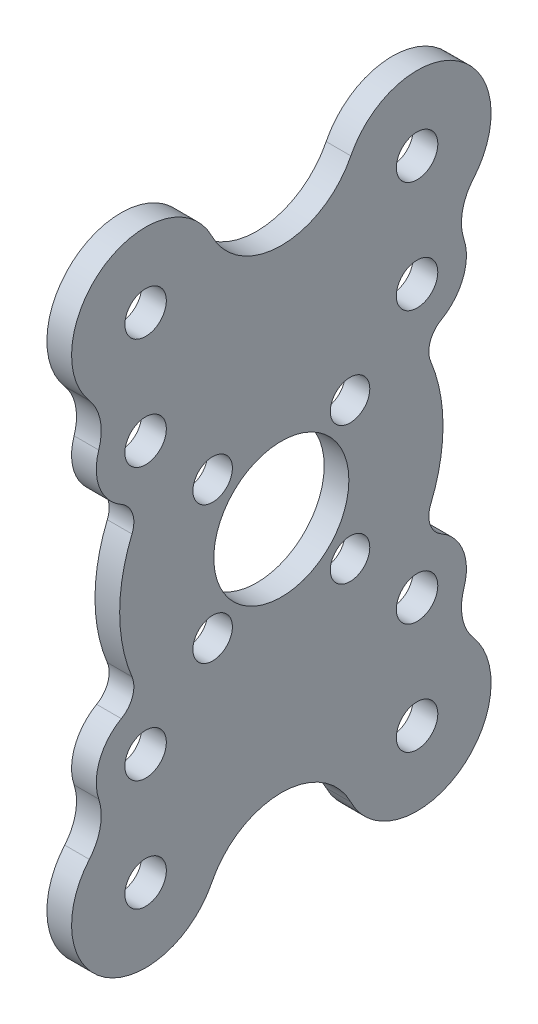
SolidWorks part; units mm, degrees
material "AR500"
ref_plane "Front Plane" through (0, 0, 0) normal (0, 0, 1) x (1, 0, 0)
ref_plane "Top Plane" through (0, 0, 0) normal (0, 1, 0) x (1, 0, 0)
ref_plane "Right Plane" through (0, 0, 0) normal (1, 0, 0) x (0, 0, -1)
ref_plane "Motor Front Plane" through (39.075, 0, 0) normal (1, 0, 0) x (0, 0, -1)
sketch "Sketch1" plane through (39.075, 0, 0) normal (1, 0, 0) x (0, 0, -1)
  line L0 (0, -17.4625) -> (0, 0) construction
  line L1 (17.4625, 17.4625) -> (-17.4625, 17.4625) construction
  line L2 (17.4625, 17.4625) -> (17.4625, -17.4625) construction
  line L3 (17.4625, -17.4625) -> (-17.4625, -17.4625) construction
  line L4 (-17.4625, 17.4625) -> (-17.4625, -17.4625) construction
  line L6 (17.4625, 0) -> (0, 0) construction
  circle A0 centre (8.8388, -8.8388) radius 1.65 construction
  circle A1 centre (8.8388, 8.8388) radius 1.65 construction
  circle A2 centre (-8.8388, -8.8388) radius 1.65 construction
  circle A3 centre (-8.8388, 8.8388) radius 1.65 construction
  circle A4 centre (8.8388, -8.8388) radius 1.65 construction
  circle A5 centre (8.8388, 8.8388) radius 1.65 construction
  circle A6 centre (-8.8388, -8.8388) radius 1.65 construction
  circle A7 centre (-8.8388, 8.8388) radius 1.65 construction
  circle A8 centre (0, 0) radius 20.8 construction
  circle A9 centre (0, 0) radius 8.69
  circle A10 centre (-8.8388, 8.8388) radius 2.54
  circle A11 centre (8.8388, 8.8388) radius 2.54
  circle A12 centre (8.8388, -8.8388) radius 2.54
  circle A13 centre (-8.8388, -8.8388) radius 2.54
  circle A14 centre (-8.8388, 8.8388) radius 3.81 construction
  circle A15 centre (17.4625, 17.4625) radius 3.8957 construction
  circle A16 centre (17.4625, 17.4625) radius 2.667
  circle A17 centre (17.4625, -17.4625) radius 2.667
  circle A18 centre (-17.4625, -17.4625) radius 2.667
  circle A19 centre (-17.4625, 17.4625) radius 2.667
  arc A20 (-17.582, 11.1136) -> (-17.582, -11.1136) centre (0, 0) ccw
  arc A21 (-11.1136, 17.582) -> (11.1136, 17.582) centre (0, 0) cw
  arc A22 (17.582, 11.1136) -> (17.582, -11.1136) centre (0, 0) cw
  arc A23 (11.1136, -17.582) -> (-11.1136, -17.582) centre (0, 0) cw
  arc A24 (-17.582, 11.1136) -> (-11.1136, 17.582) centre (-17.4625, 17.4625) cw
  arc A25 (11.1136, 17.582) -> (17.582, 11.1136) centre (17.4625, 17.4625) cw
  arc A26 (17.582, -11.1136) -> (11.1136, -17.582) centre (17.4625, -17.4625) cw
  arc A27 (-17.582, -11.1136) -> (-11.1136, -17.582) centre (-17.4625, -17.4625) ccw
  dimension "D1" = 41.6
  dimension "D2" = 5.08
  dimension "D3" = 7.62
  dimension "D4" = 5.334
  dimension "D6" = 6.35
  dimension "D5" = 34.925
extrude "Boss-Extrude1" add sketch "Sketch1" along normal blind 3.175
fillet "Fillet1" radius 3.175 8 edges at (40.6625, 17.582, 11.1136) (40.6625, 11.1136, -17.582) (40.6625, -11.1136, -17.582) (40.6625, -17.582, -11.1136) (40.6625, -17.582, 11.1136) (40.6625, -11.1136, 17.582) (40.6625, 11.1136, 17.582) (40.6625, 17.582, -11.1136)
sketch "Sketch2" plane through (42.25, 0, 0) normal (1, 0, 0) x (0, 0, -1)
  line L0 (-17.4625, -31.75) -> (-17.4625, 31.75) construction
  line L5 (0, 0) -> (-17.4625, 0) construction
  line L6 (0, 0) -> (0, 30.48) construction
  arc A24 (-8.9422, 36.0079) -> (-20.8359, 22.8424) centre (-17.4625, 31.75) ccw
  circle A27 centre (-17.4625, 31.75) radius 2.667
  circle A32 centre (17.4625, 31.75) radius 2.667
  arc A33 (8.9422, 36.0079) -> (20.8359, 22.8424) centre (17.4625, 31.75) cw
  circle A34 centre (-17.4625, 17.4625) radius 2.667 construction
  arc A35 (-8.9422, 36.0079) -> (8.9422, 36.0079) centre (0, 40.4766) ccw
  arc A36 (-20.8359, 22.8424) -> (20.8359, 22.8424) centre (0, 49.6538) ccw
  arc A37 (-11.9352, 20.5884) -> (-20.5884, 11.9352) centre (-17.4625, 17.4625) ccw construction
  arc A38 (20.5884, 11.9352) -> (11.9352, 20.5884) centre (17.4625, 17.4625) ccw construction
  point P1 (0, 0)
  point P3 (-17.4625, 17.4625)
  point P20 (0, 0)
  point P24 (0, 0)
  dimension "D3" = 30.48
  dimension "D1" = 19.05
  dimension "D2" = 63.5
extrude "Boss-Extrude2" add sketch "Sketch2" against normal up to surface (3.175 mm away) up to face at (39.075, -17.4625, 14.7955)
mirror "Mirror1" about plane through (0, 0, 0) normal (0, 1, 0) of "Boss-Extrude2"
fillet "Fillet2" radius 6.35 4 edges at (40.6625, 22.8424, -20.8359) (40.6625, -22.8424, 20.8359) (40.6625, -22.8424, -20.8359) (40.6625, 22.8424, 20.8359)
equation "\"D1@Sketch1\"=41.6mm"
